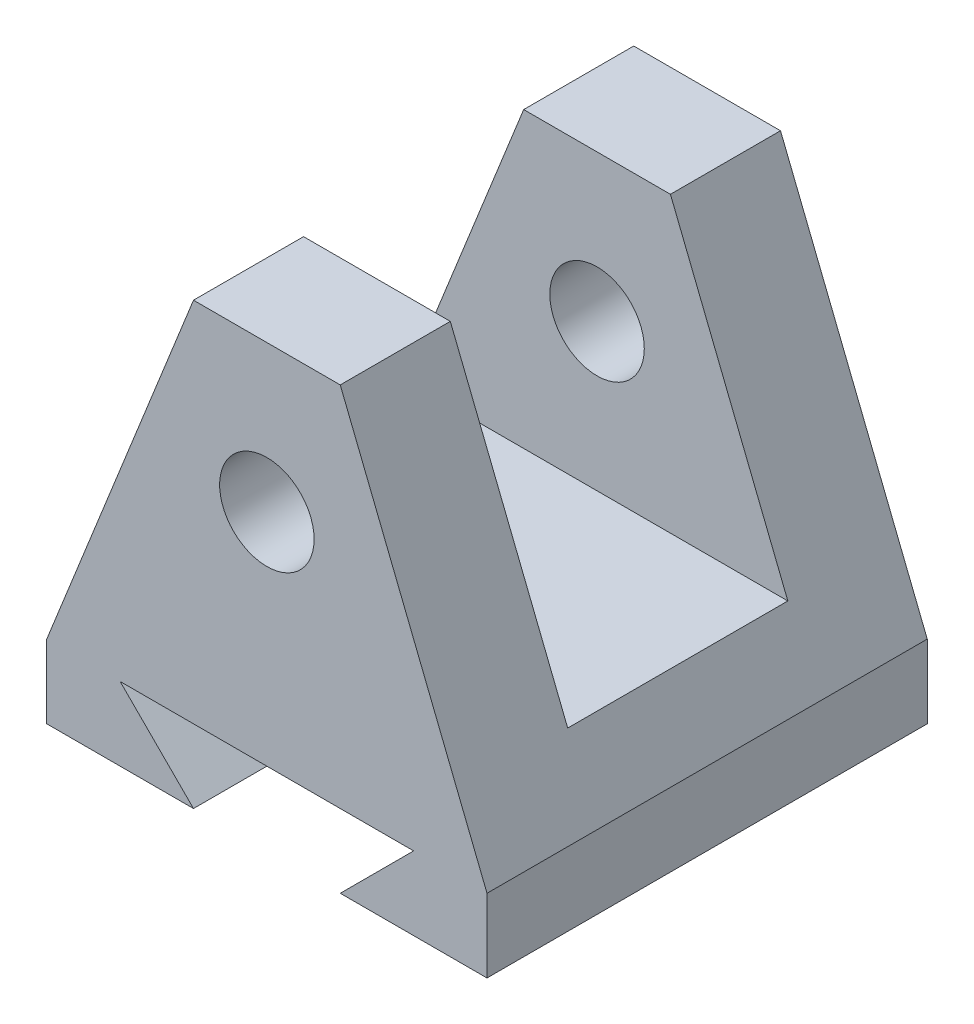
SolidWorks part; units mm, degrees
ref_plane "Front" through (0, 0, 0) normal (0, 0, 1) x (1, 0, 0)
ref_plane "Top" through (0, 0, 0) normal (0, 1, 0) x (1, 0, 0)
ref_plane "Right" through (0, 0, 0) normal (1, 0, 0) x (0, 0, -1)
ref_axis "Axis1" through (-84.4107, 0, 0) along (1, 0, 0)
ref_axis "Axis2" through (0, 64.3378, 0) along (0, -1, 0)
ref_axis "Axis3" through (0, 0, -102.329) along (0, 0, 1)
sketch "Sketch2" plane through (0, 0, 0) normal (0, 0, 1) x (1, 0, 0)
  line L0 (-30, -10) -> (-30, 0)
  line L1 (-30, 0) -> (-10, 50)
  line L2 (-10, 50) -> (10, 50)
  line L3 (10, 50) -> (30, 0)
  line L4 (30, 0) -> (30, -10)
  line L5 (30, -10) -> (10, -10)
  line L6 (10, -10) -> (20, 0)
  line L7 (20, 0) -> (-20, 0)
  line L8 (-20, 0) -> (-10, -10)
  line L9 (-10, -10) -> (-30, -10)
  point P2 (0, 50)
  dimension "D1" = 20
  dimension "D2" = 20
  dimension "D3" = 10
  dimension "D4" = 10
  dimension "D5" = 60
  dimension "D6" = 45
  dimension "D7" = 45
  dimension "D8" = 60
  dimension "D9" = 20
extrude "Boss-Extrude1" add sketch "Sketch2" along normal blind 60
sketch "Sketch3" plane through (0, 0, 60) normal (0, 0, 1) x (1, 0, 0)
  line L0 (-30, -10) -> (-10, -10) construction
  circle A0 centre (0, 30) radius 6.4362
  point P2 (0, 0)
  dimension "D1" = 12.8724
  dimension "D2" = 40
extrude "Cut-Extrude1" cut sketch "Sketch3" against normal through all
ref_plane "Plane1" through (30, 0, 60) normal (0, 0, -1) x (-1, 0, 0)
sketch "Sketch9" plane through (30, 0, 0) normal (1, 0, 0) x (0, 0, -1)
  line L0 (-45, 50) -> (-45, 10)
  line L1 (-60, 50) -> (0, 50) construction
  line L2 (-45, 10) -> (-15, 10)
  line L3 (-15, 10) -> (-15, 50)
  line L4 (-15, 50) -> (-45, 50)
  line L5 (-60, -10) -> (0, -10) construction
  dimension "D1" = 15
  dimension "D2" = 15
  dimension "D3" = 20
extrude "Cut-Extrude3" cut sketch "Sketch9" against normal through all
